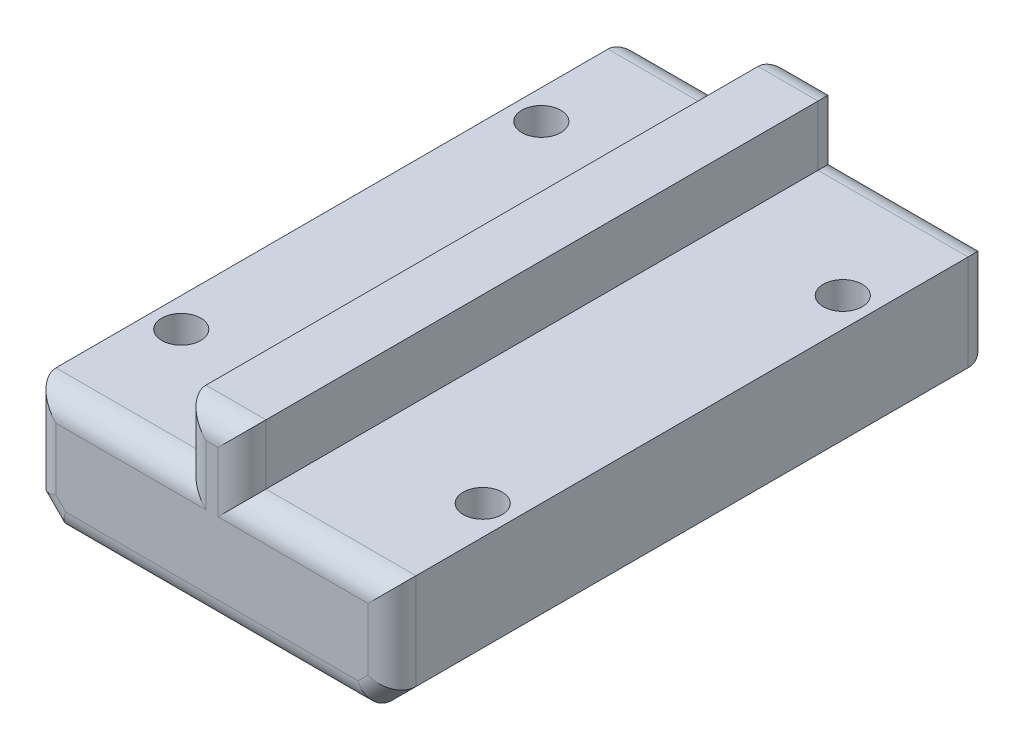
SolidWorks part; units mm, degrees
ref_plane "Front Plane" through (0, 0, 0) normal (0, 0, 1) x (1, 0, 0)
ref_plane "Top Plane" through (0, 0, 0) normal (0, 1, 0) x (1, 0, 0)
ref_plane "Right Plane" through (0, 0, 0) normal (1, 0, 0) x (0, 0, -1)
sketch "Sketch1" plane through (0, 0, 0) normal (0, 1, 0) x (1, 0, 0)
  line L1 (-15, -25) -> (15, -25)
  line L2 (-15, -25) -> (-15, 25)
  line L3 (-15, 25) -> (15, 25)
  line L4 (15, -25) -> (15, 25)
  line L5 (-15, -25) -> (15, 25) construction
  line L6 (-15, 25) -> (15, -25) construction
  point P0 (0, 0)
  dimension "D1" = 30
  dimension "D2" = 50
extrude "Boss-Extrude1" add sketch "Sketch1" along normal blind 10
sketch "Sketch2" plane through (0, 10, 0) normal (0, 1, 0) x (1, 0, 0)
  line L0 (15, 25) -> (-15, 25) construction
  line L1 (-2.5, -25) -> (2.5, -25)
  line L2 (-2.5, -25) -> (-2.5, 25)
  line L3 (-2.5, 25) -> (2.5, 25)
  line L4 (2.5, -25) -> (2.5, 25)
  line L5 (-2.5, -25) -> (2.5, 25) construction
  line L6 (-2.5, 25) -> (2.5, -25) construction
  point P0 (0, 0)
  dimension "D1" = 5
extrude "Boss-Extrude2" add sketch "Sketch2" along normal blind 5
sketch "Sketch3" plane through (0, 0, 0) normal (0, -1, 0) x (1, 0, 0)
  line L0 (-12.56, -25) -> (-12.56, -15) construction
  line L1 (15, -25) -> (-15, -25) construction
  line L2 (12.56, -25) -> (12.56, -15) construction
  line L3 (12.56, 25) -> (12.56, 15) construction
  line L4 (-15, 25) -> (15, 25) construction
  line L5 (-12.56, 25) -> (-12.56, 15) construction
  line L6 (-15, -25) -> (-15, 25) construction
  line L7 (15, 25) -> (15, -25) construction
  circle A0 centre (-12.56, 15) radius 1.625
  circle A1 centre (-12.56, -15) radius 1.625
  circle A2 centre (12.56, -15) radius 1.625
  circle A3 centre (12.56, 15) radius 1.625
  dimension "D7" = 3.25
  dimension "D8" = 3.25
  dimension "D9" = 3.25
  dimension "D10" = 3.25
  dimension "D1" = 10
  dimension "D2" = 2.44
  dimension "D3" = 2.44
  dimension "D4" = 10
  dimension "D5" = 10
  dimension "D6" = 10
extrude "Cut-Extrude1" cut sketch "Sketch3" against normal through all
sketch "Sketch4" plane through (0, 0, 0) normal (0, -1, 0) x (1, 0, 0)
  circle A0 centre (-12.56, 15) radius 2.7
  circle A1 centre (-12.56, -15) radius 2.7
  circle A2 centre (12.56, -15) radius 2.7
  circle A3 centre (12.56, 15) radius 2.7
  dimension "D1" = 5.4
  dimension "D2" = 5.4
  dimension "D3" = 5.4
  dimension "D4" = 5.4
extrude "Cut-Extrude2" cut sketch "Sketch4" against normal blind 1.45
chamfer "Chamfer1" distance 2 angle 45 1 edges at (-15, 0, 0)
chamfer "Chamfer2" distance 2 angle 45 1 edges at (15, 0, 0)
fillet "Fillet1" radius 2 10 edges at (-14, 1, 25) (-15, 6, 25) (0, 15, 25) (15, 6, 25) (14, 1, 25) (0, 0, 25)
fillet "Fillet2" radius 2 10 edges at (0, 15, -25) (-15, 6, -25) (-14, 1, -25) (0, 0, -25) (14, 1, -25) (15, 6, -25)
sketch "Mobious Logo" plane through (0, 0, 0) normal (0, -1, 0) x (1, 0, 0)
  line L0 (-3.7255, 6.3776) -> (-4.8288, 6.3776)
  line L1 (-4.8288, 6.3776) -> (-8.8122, -0.4671)
  line L2 (-8.8122, -0.4671) -> (-2.3229, -0.4671)
  line L3 (-2.3229, -0.4671) -> (-2.9078, 0.6781)
  line L4 (-2.9078, 0.6781) -> (-7.1291, 0.6781)
  line L5 (-7.1291, 0.6781) -> (-3.7255, 6.3776)
  line L6 (-3.9312, 2.9178) -> (-3.4262, 3.7407)
  line L7 (-3.4262, 3.7407) -> (-0.2096, -1.8884)
  line L8 (-0.2096, -1.8884) -> (-8.5691, -1.8884)
  line L9 (-8.5691, -1.8884) -> (-8.8164, -0.785)
  line L10 (-8.8164, -0.785) -> (-1.6983, -0.785)
  line L11 (-1.6983, -0.785) -> (-3.9312, 2.9178)
  line L12 (-6.5494, 1.0103) -> (-3.4262, 6.2092)
  line L13 (-3.4262, 6.2092) -> (0.127, 0)
  line L14 (0.127, 0) -> (3.6616, 6.2092)
  line L15 (3.6616, 6.2092) -> (6.6367, 1.0103)
  line L16 (6.6367, 1.0103) -> (5.5735, 1.0103)
  line L17 (5.5735, 1.0103) -> (3.6616, 4.3513)
  line L18 (3.6616, 4.3513) -> (0.1736, -1.776)
  line L19 (0.1736, -1.776) -> (-3.4262, 4.5147)
  line L20 (-3.4262, 4.5147) -> (-5.4211, 1.0103)
  line L21 (-5.4211, 1.0103) -> (-6.5494, 1.0103)
  line L22 (3.9795, 6.3776) -> (5.0268, 6.3776)
  line L23 (5.0268, 6.3776) -> (8.9727, -0.4671)
  line L24 (8.9727, -0.4671) -> (2.4647, -0.4671)
  line L25 (2.4647, -0.4671) -> (3.194, 0.6781)
  line L26 (3.194, 0.6781) -> (7.2522, 0.6781)
  line L27 (7.2522, 0.6781) -> (3.9795, 6.3776)
  line L28 (3.6616, 3.7407) -> (0.4262, -1.8884)
  line L29 (0.4262, -1.8884) -> (8.6735, -1.8884)
  line L30 (8.6735, -1.8884) -> (9.1111, -0.785)
  line L31 (9.1111, -0.785) -> (1.9036, -0.785)
  line L32 (1.9036, -0.785) -> (4.056, 2.9598)
  line L33 (4.056, 2.9598) -> (3.6616, 3.7407)
extrude "Cut-Extrude6" cut sketch "Mobious Logo" against normal blind 1
